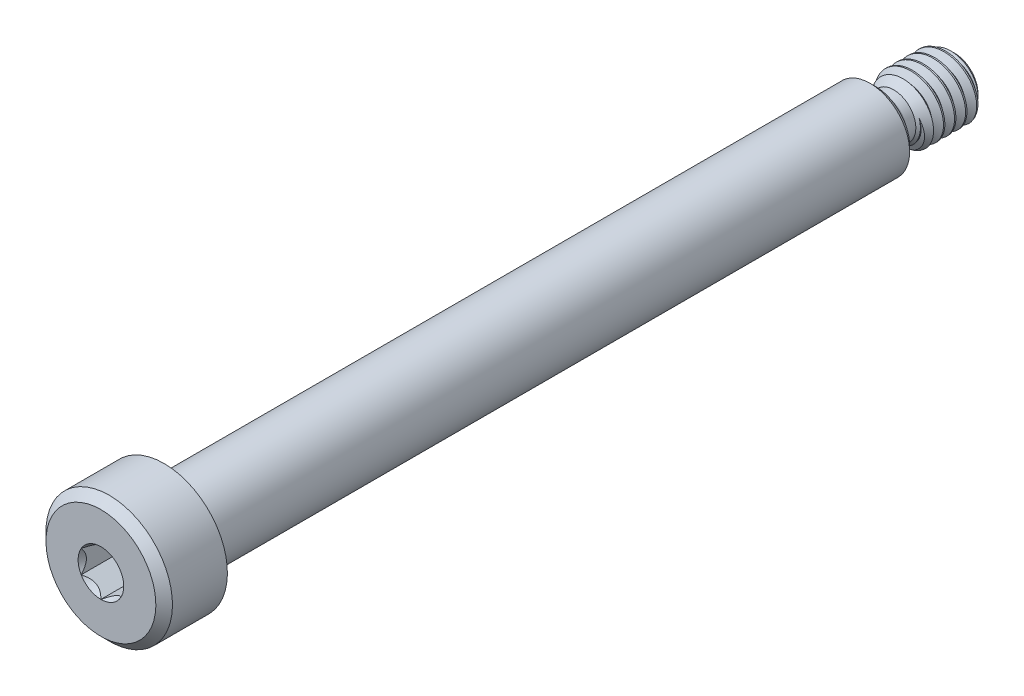
SolidWorks part; units mm, degrees
material "Stainless Steel (ferritic)"
ref_plane "Front Plane" through (0, 0, 0) normal (0, 0, 1) x (1, 0, 0)
ref_plane "Top Plane" through (0, 0, 0) normal (0, 1, 0) x (1, 0, 0)
ref_plane "Right Plane" through (0, 0, 0) normal (1, 0, 0) x (0, 0, -1)
sketch "Sketch1" plane through (0, 0, 0) normal (1, 0, 0) x (0, 0, -1)
  line L0 (0, 0) -> (50, 0) construction
  line L1 (0, 0) -> (-4, 0) construction
  line L2 (50, 2) -> (50, -2) construction
  line L3 (50, 2) -> (50.7, 2) construction
  line L4 (-4, -4) -> (-4, 4) construction
  line L5 (50, 2) -> (45, 2) construction
  line L6 (0, 2.5) -> (45, 2.5) construction
  line L7 (45, 2.5) -> (45, -2.5) construction
  line L8 (0, 4) -> (0, -4) construction
  line L9 (-4, 1.25) -> (-4, -1.25) construction
  line L10 (46.143, 1.4) -> (46.143, -1.4) construction
  line L11 (45, -2.5) -> (0, -2.5) construction
  point P6 (-4, 0)
  point P9 (50, 0)
  point P13 (46.143, 2)
  point P15 (45, 0)
  point P16 (0, 0)
  point P22 (-4, 0)
  point P25 (46.143, 0)
  point P26 (48.25, -2)
  point P28 (3.75, 0)
  point P29 (41.25, 0)
  dimension "Thread Pitch" = 0.7
  dimension "Thread Size" = 4
  dimension "Thread Length" = 5
  dimension "Clearance Length" = 1.143
  dimension "Shoulder Diameter" = 5
  dimension "Head Height" = 4
  dimension "Head Diameter" = 8
  dimension "Drive Size" = 2.5
  dimension "Clearance Diameter" = 2.8
  dimension "Shoulder Length" = 45
  dimension "D1" = 1.75
  dimension "D2" = 3.75
  dimension "D3" = 3.75
ref_plane "Plane1" through (0, 0, 4) normal (0, 0, 1) x (1, 0, 0)
sketch "Sketch2" plane through (0, 0, 4) normal (0, 0, 1) x (1, 0, 0)
  line L0 (0, 1.25) -> (0, -1.25) construction
  line L1 (0, 1.4434) -> (-1.25, 0.7217) construction
  line L2 (-1.25, 0.7217) -> (-1.25, -0.7217) construction
  line L3 (-1.25, -0.7217) -> (0, -1.4434) construction
  line L4 (0, -1.4434) -> (1.25, -0.7217) construction
  line L5 (1.25, -0.7217) -> (1.25, 0.7217) construction
  line L6 (1.25, 0.7217) -> (0, 1.4434) construction
  line L7 (-4, 0) -> (4, 0) construction
  line L10 (0, -4) -> (0, 4) construction
  circle A0 centre (0, 0) radius 1.25 construction
  circle A1 centre (0, 0) radius 4 construction
  point P10 (0, 0)
sketch "Sketch3" plane through (0, 0, 0) normal (1, 0, 0) x (0, 0, -1)
  line L0 (50, 0) -> (-4, 0)
  line L3 (0, 4) -> (0, 2.5)
  line L5 (45, 2.5) -> (45, 1.4) construction
  line L6 (45, 2.5) -> (45, -2.5) construction
  line L8 (46.143, 1.4) -> (46.743, 2)
  line L9 (50, 2) -> (45, 2) construction
  line L10 (46.743, 2) -> (49.475, 2)
  line L11 (49.475, 2) -> (50, 1.475)
  line L12 (50, 2) -> (50, -2) construction
  line L13 (50, 1.475) -> (50, 0)
  line L15 (45, 1.4) -> (45.2858, 1.4) construction
  line L16 (45.2858, 1.4) -> (45.5715, 1.4) construction
  line L17 (45.5715, 1.4) -> (45.8572, 1.4) construction
  line L18 (45.8572, 1.4) -> (46.143, 1.4) construction
  line L20 (-4, 0) -> (-4, 3.475)
  line L21 (-4, -4) -> (-4, 4) construction
  line L22 (-4, 3.475) -> (-3.475, 4)
  line L23 (-3.475, 4) -> (0, 4)
  line L24 (45.5715, 1.4) -> (46.143, 1.4)
  line L26 (45, 1.9715) -> (45, 2.15)
  line L27 (45, 2.15) -> (44.65, 2.5)
  line L28 (0, 2.5) -> (45, 2.5) construction
  line L29 (44.65, 2.5) -> (0, 2.5)
  arc A1 (45.5715, 1.4) -> (45, 1.9715) centre (45.5715, 1.9715) cw
  dimension "D1" = 45
  dimension "D2" = 45
  dimension "D3" = 0.525
  dimension "D4" = 45
  dimension "D5" = 45
  dimension "D6" = 0.35
revolve "Revolve2" add sketch "Sketch3" angle 360 about L0
sketch "Sketch4" plane through (0, 0, 4) normal (0, 0, 1) x (1, 0, 0)
  line L1 (0, 1.4434) -> (-1.25, 0.7217)
  line L2 (-1.25, 0.7217) -> (-1.25, -0.7217)
  line L3 (-1.25, -0.7217) -> (0, -1.4434)
  line L4 (0, -1.4434) -> (1.25, -0.7217)
  line L5 (1.25, -0.7217) -> (1.25, 0.7217)
  line L6 (1.25, 0.7217) -> (0, 1.4434)
  circle A0 centre (0, 0) radius 1.25 construction
extrude "Cut-Extrude1" cut sketch "Sketch4" against normal blind 2.2
sketch "Sketch5" plane through (0, 0, 4) normal (0, 0, 1) x (1, 0, 0)
  circle A0 centre (0, 0) radius 1.4434
extrude "Cut-Extrude2" cut sketch "Sketch5" against normal blind 2 draft 30
ref_plane "Plane2" through (0, 0, -46.143) normal (0, 0, 1) x (1, 0, 0)
ref_plane "Plane3" through (0, 0, -50) normal (0, 0, 1) x (1, 0, 0)
split "Split1" trim tools "Plane2" bodies to split 106 resulting bodies 107 108
sketch "Sketch6" plane through (0, 0, -50) normal (0, 0, 1) x (1, 0, 0)
  circle A0 centre (0, 0) radius 2
curve "Helix/Spiral1" pitch 0.7 height 5 radius 2 centre (0, 0, -50) axis (0, 0, 1) start towards (0, 1, 0)
sketch "Sketch7" plane through (0, 0, 0) normal (1, 0, 0) x (0, 0, -1)
  line L0 (49.9562, 2.0758) -> (50.6562, 2.0758) construction
  line L1 (50.6562, 2.0758) -> (50.3062, 1.4696) construction
  line L2 (50.3062, 1.4696) -> (49.9562, 2.0758) construction
  line L3 (50.3062, 1.4696) -> (50.3062, 1.5453) construction
  line L4 (50.3062, 1.5453) -> (50.3062, 2) construction
  line L5 (50.3062, 2) -> (50.3062, 2.0758) construction
  line L6 (50.2625, 1.5453) -> (50.35, 1.5453) construction
  line L7 (50.2625, 1.5453) -> (50.35, 1.5453)
  line L8 (50.6125, 2) -> (50, 2) construction
  line L9 (50.35, 1.5453) -> (50.6344, 2.0379)
  line L10 (49.9781, 2.0379) -> (50.6344, 2.0379) construction
  line L11 (50.6344, 2.0379) -> (49.9781, 2.0379)
  line L12 (49.9781, 2.0379) -> (50.2625, 1.5453)
  point P8 (50.3062, 1.5453)
  point P14 (50.3062, 2)
  point P17 (50.3062, 2.0379)
  point P18 (50.3062, 2.0379)
  dimension "D1" = 0.7
  dimension "D2" = 0.0875
sweep "Cut-Sweep1" cut profiles "Sketch7" path "Helix/Spiral1" align with end faces yes
sketch "Sketch8" plane through (0, 0, -46.143) normal (0, 0, 1) x (1, 0, 0)
  circle A0 centre (0, 0) radius 1.4 construction
  circle A1 centre (0, 0) radius 1.4
extrude "Boss-Extrude1" add sketch "Sketch8" against normal blind 0.5 draft 30
equation "\"D3@Sketch3\"=\"Thread Pitch@Sketch1\"*.75"
equation "\"D1@Cut-Extrude1\"=\"Head Height@Sketch1\"*.55"
equation "\"D1@Cut-Extrude2\"=\"Head Height@Sketch1\"*.5"
equation "\"D6@Sketch3\"=\"Thread Pitch@Sketch1\"*.5"
equation "\"D3@Helix/Spiral1\"=\"Thread Length@Sketch1\""
equation "\"D4@Helix/Spiral1\"=\"Thread Pitch@Sketch1\""
equation "\"D1@Sketch7\"=\"Thread Pitch@Sketch1\""
equation "\"D2@Sketch7\"=\"D1@Sketch7\"/8"
equation "\"D1@Sketch1\"=\"Thread Pitch@Sketch1\"*2.5"
equation "\"D2@Sketch1\"=\"Shoulder Diameter@Sketch1\"*.75"
equation "\"D3@Sketch1\"=\"D2@Sketch1\""
equation "\"D1@Boss-Extrude1\"=\"Thread Length@Sketch1\"/10"
